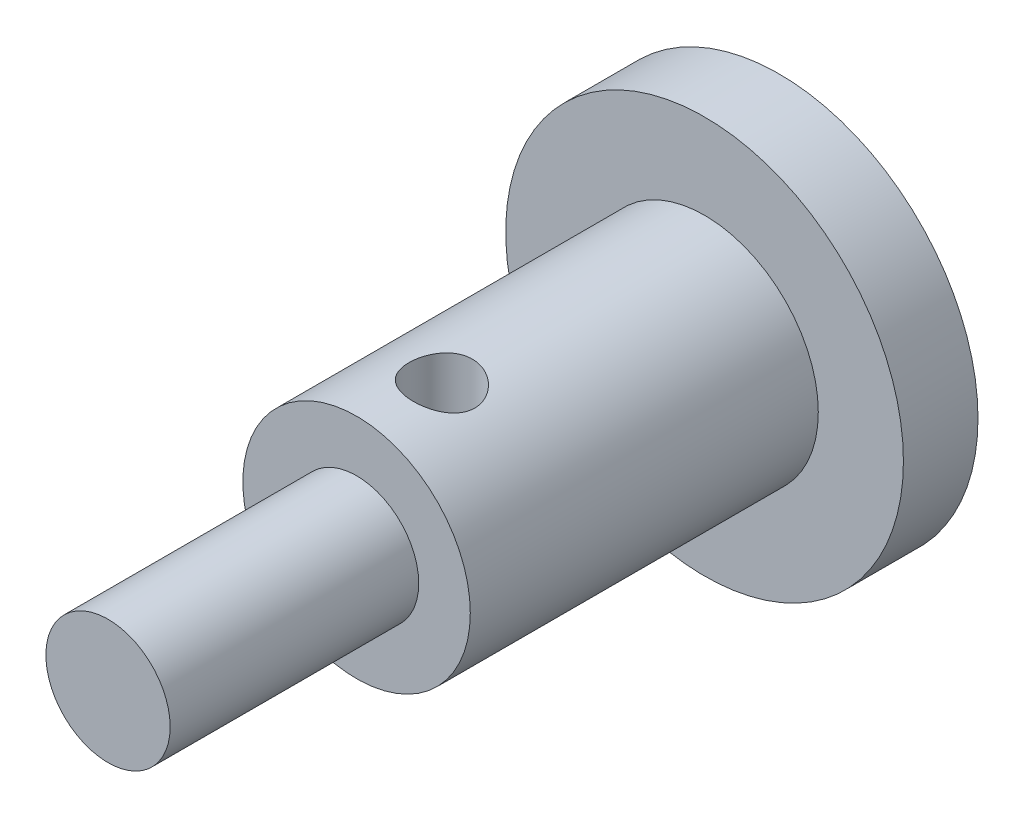
SolidWorks part; units mm, degrees
ref_plane "Front Plane" through (0, 0, 0) normal (0, 0, 1) x (1, 0, 0)
ref_plane "Top Plane" through (0, 0, 0) normal (0, 1, 0) x (1, 0, 0)
ref_plane "Right Plane" through (0, 0, 0) normal (1, 0, 0) x (0, 0, -1)
sketch "Sketch1" plane through (0, 0, 0) normal (0, 0, 1) x (1, 0, 0)
  circle A0 centre (0, 0) radius 8
  dimension "D1" = 16
extrude "Boss-Extrude1" add sketch "Sketch1" along normal blind 3
sketch "Sketch2" plane through (0, 0, 3) normal (0, 0, 1) x (1, 0, 0)
  circle A0 centre (0, 0) radius 4.575
  dimension "D1" = 9.15
extrude "Boss-Extrude2" add sketch "Sketch2" along normal blind 14
sketch "Sketch3" plane through (0, 0, 17) normal (0, 0, 1) x (1, 0, 0)
  circle A0 centre (0, 0) radius 2.5
  dimension "D1" = 5
extrude "Boss-Extrude3" add sketch "Sketch3" along normal blind 10
sketch "Sketch4" plane through (0, 0, 0) normal (0, 1, 0) x (1, 0, 0)
  line L0 (-4.575, -3) -> (-4.575, -17) construction
  circle A0 centre (0.425, -13.9935) radius 1.325
  dimension "D2" = 2.65
  dimension "D1" = 5
  dimension "D3" = 14
extrude "Cut-Extrude1" cut sketch "Sketch4" against normal mid plane 15
equation "\"D1@Sketch2\"= 9.35 - \"tol1@parametersSketch@prostheticParameters.SLDPRT\""
equation "\"D2@Sketch4\"= 2.45 + \"tol1@parametersSketch@prostheticParameters.SLDPRT\""
